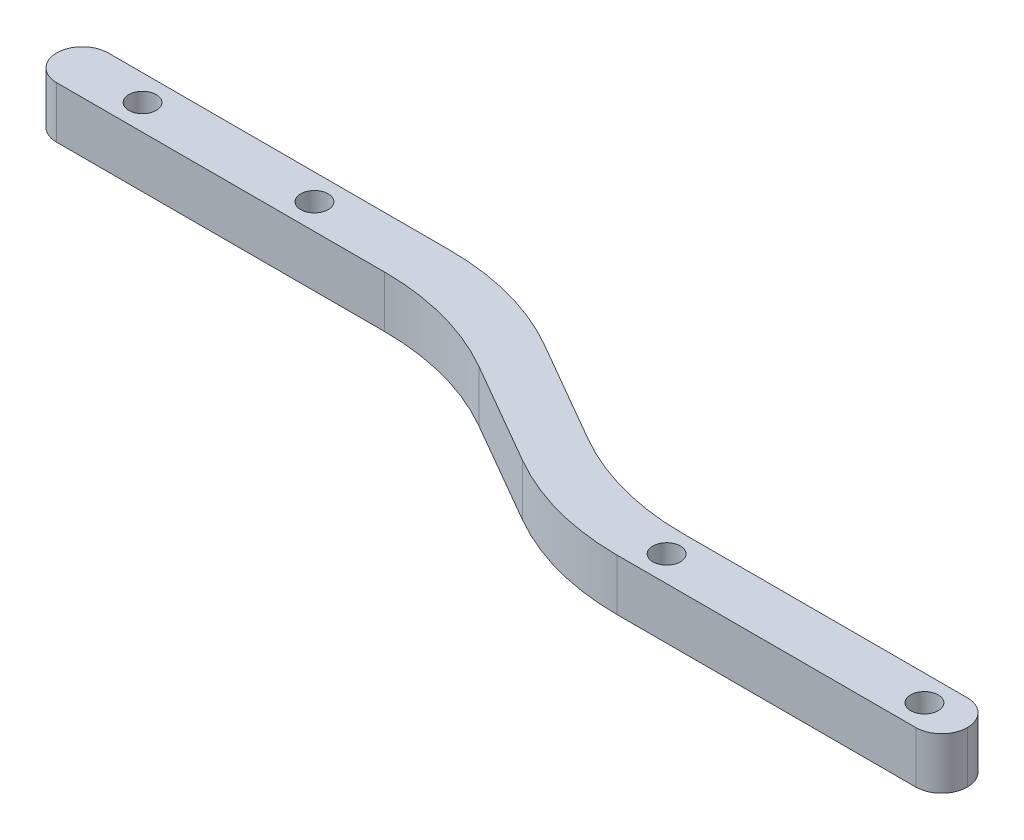
SolidWorks part; units mm, degrees
ref_plane "Front Plane" through (0, 0, 0) normal (0, 0, 1) x (1, 0, 0)
ref_plane "Top Plane" through (0, 0, 0) normal (0, 1, 0) x (1, 0, 0)
ref_plane "Right Plane" through (0, 0, 0) normal (1, 0, 0) x (0, 0, -1)
sketch "Sketch1" plane through (0, 0, 0) normal (0, 1, 0) x (1, 0, 0)
  line L6 (22.0981, 0) -> (-22.0981, 0)
  line L7 (-22.0981, 0) -> (-48.0788, 15)
  line L8 (-48.0788, 15) -> (-98.8827, 15)
  line L9 (-98.8827, 15) -> (-98.8827, 9)
  line L10 (-98.8827, 9) -> (-49.6865, 9)
  line L11 (-49.6865, 9) -> (-23.7058, -6)
  line L12 (-23.7058, -6) -> (22.0981, -6)
  line L13 (22.0981, -6) -> (22.0981, 0)
  line L14 (-28.5756, 3.7398) -> (-31.5756, -1.4564) construction
  line L15 (-22.0981, 0) -> (-23.7058, -6) construction
  line L16 (-48.0788, 15) -> (-49.6865, 9) construction
  point P4 (0, 0)
  point P15 (-22.9019, -3)
  point P16 (-48.8827, 12)
  dimension "D1" = 6
  dimension "D2" = 45
  dimension "D3" = 50
  dimension "D4" = 30
  dimension "D5" = 30
extrude "Boss-Extrude1" add sketch "Sketch1" along normal mid plane 6
sketch "Sketch2" plane through (0, 3, 0) normal (0, 1, 0) x (1, 0, 0)
  line L0 (22.0981, -6) -> (22.0981, 0) construction
  line L1 (-98.8827, 15) -> (-98.8827, 9) construction
  circle A0 centre (17.0981, -3) radius 1.6
  circle A1 centre (-12.9019, -3) radius 1.6
  circle A2 centre (-68.8827, 12) radius 1.6
  circle A3 centre (-88.8827, 12) radius 1.6
  point P7 (22.0981, -3)
  point P14 (-98.8827, 12)
  dimension "D1" = 3.2
  dimension "D2" = 30
  dimension "D3" = 5
  dimension "D4" = 10
  dimension "D5" = 20
extrude "Cut-Extrude1" cut sketch "Sketch2" against normal through all
fillet "Fillet1" radius 30 4 edges at (-23.7058, 0, 6) (-49.6865, 0, -9) (-48.0788, 0, -15) (-22.0981, 0, 0)
fillet "Fillet2" radius 3 4 edges at (-98.8827, 0, -9) (-98.8827, 0, -15) (22.0981, 0, 6) (22.0981, 0, 0)
